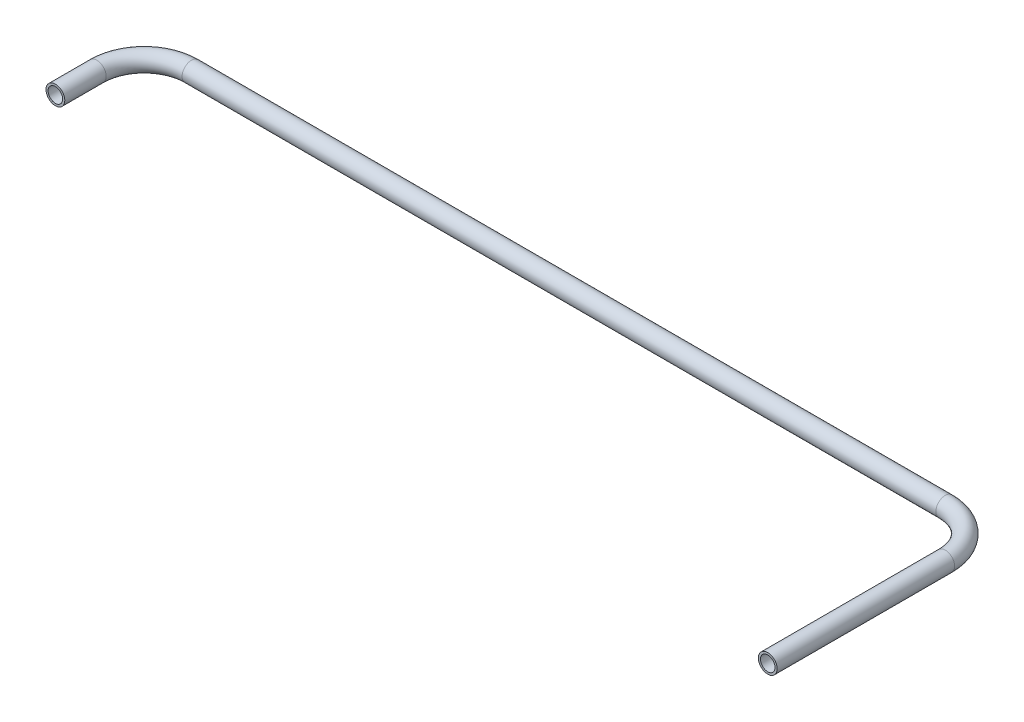
SolidWorks part; units mm, degrees
ref_plane "Front Plane" through (0, 0, 0) normal (0, 0, 1) x (1, 0, 0)
ref_plane "Top Plane" through (0, 0, 0) normal (0, 1, 0) x (1, 0, 0)
ref_plane "Right Plane" through (0, 0, 0) normal (1, 0, 0) x (0, 0, -1)
sketch "Sketch1" plane through (0, 0, 0) normal (0, 1, 0) x (1, 0, 0)
  line L0 (0, 0) -> (0, 14)
  line L1 (16, 30) -> (270.775, 30)
  line L2 (286.775, 14) -> (286.775, -46)
  arc A0 (270.775, 30) -> (286.775, 14) centre (270.775, 14) cw
  arc A1 (0, 14) -> (16, 30) centre (16, 14) cw
  dimension "D1" = 16
  dimension "D2" = 16
  dimension "D3" = 14
  dimension "D4" = 60
  dimension "D5" = 286.775
sketch "Sketch2" plane through (0, 0, 0) normal (0, 0, 1) x (1, 0, 0)
  circle A0 centre (0, 0) radius 3.175
  dimension "D1" = 6.35
sweep "Sweep-Thin1" add profiles "Sketch2" path "Sketch1" parameters "D1"=0.7112
